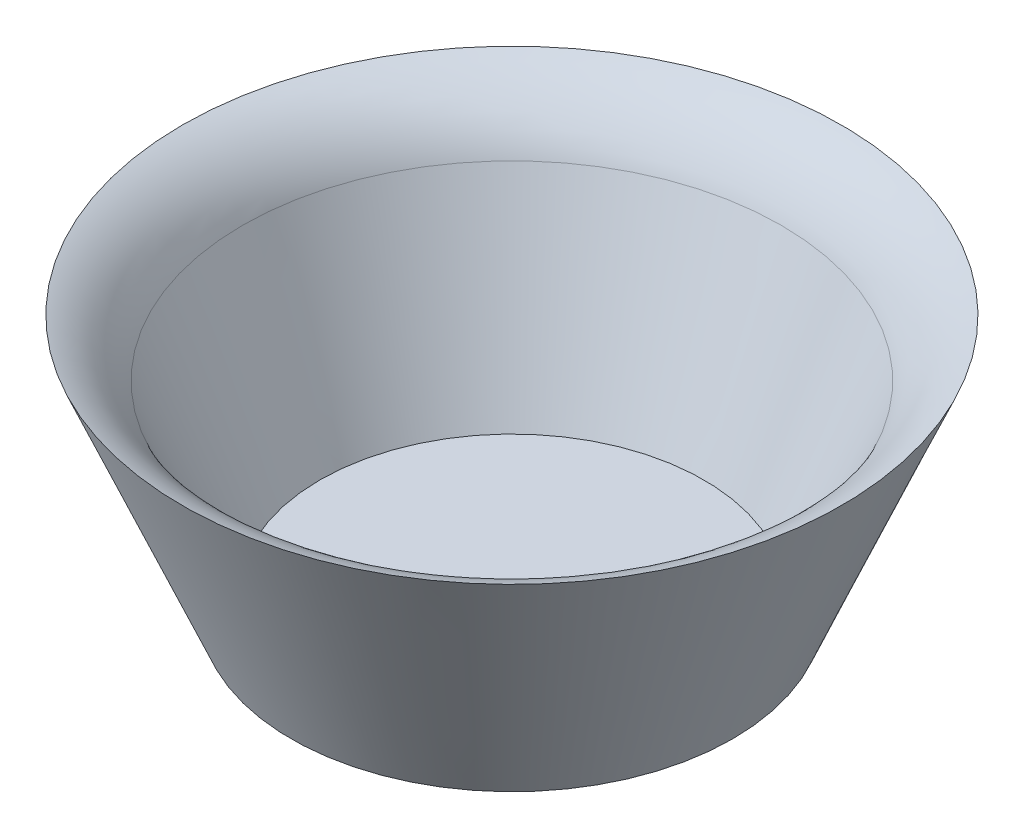
SolidWorks part; units mm, degrees
ref_plane "Front Plane" through (0, 0, 0) normal (0, 0, 1) x (1, 0, 0)
ref_plane "Top Plane" through (0, 0, 0) normal (0, 1, 0) x (1, 0, 0)
ref_plane "Right Plane" through (0, 0, 0) normal (1, 0, 0) x (0, 0, -1)
sketch "Sketch1" plane through (0, 0, 0) normal (0, 0, 1) x (1, 0, 0)
  line L0 (0, -36.8033) -> (0, -71.6035) construction
  line L1 (0, 0) -> (0, -3.5)
  line L2 (0, -3.5) -> (-43, -3.5)
  line L3 (-43, -3.5) -> (-64.2237, 46.5)
  line L4 (-64.2237, 46.5) -> (-57.1624, 46.5)
  line L5 (-57.1624, 46.5) -> (-37.4243, 0)
  line L6 (-37.4243, 0) -> (0, 0)
  line L7 (-65.5997, 28.674) -> (-65.5997, -2.1316) construction
  line L8 (-62, -6.0893) -> (-62, -51.2254) construction
  line L9 (-156.9903, 39.5) -> (-134.3111, 39.5) construction
  point P14 (-60.6931, 46.5)
  dimension "D1" = 43
  dimension "D2" = 50
  dimension "D3" = 65.5997
  dimension "D4" = 3.5
  dimension "D5" = 6.5
  dimension "D6" = 113
  dimension "D7" = 62
  dimension "D8" = 7
revolve "Revolve1" add sketch "Sketch1" angle 360 about L0
fillet "Fillet1" radius 20 1 edges at (-57.1624, 46.5, 0)
